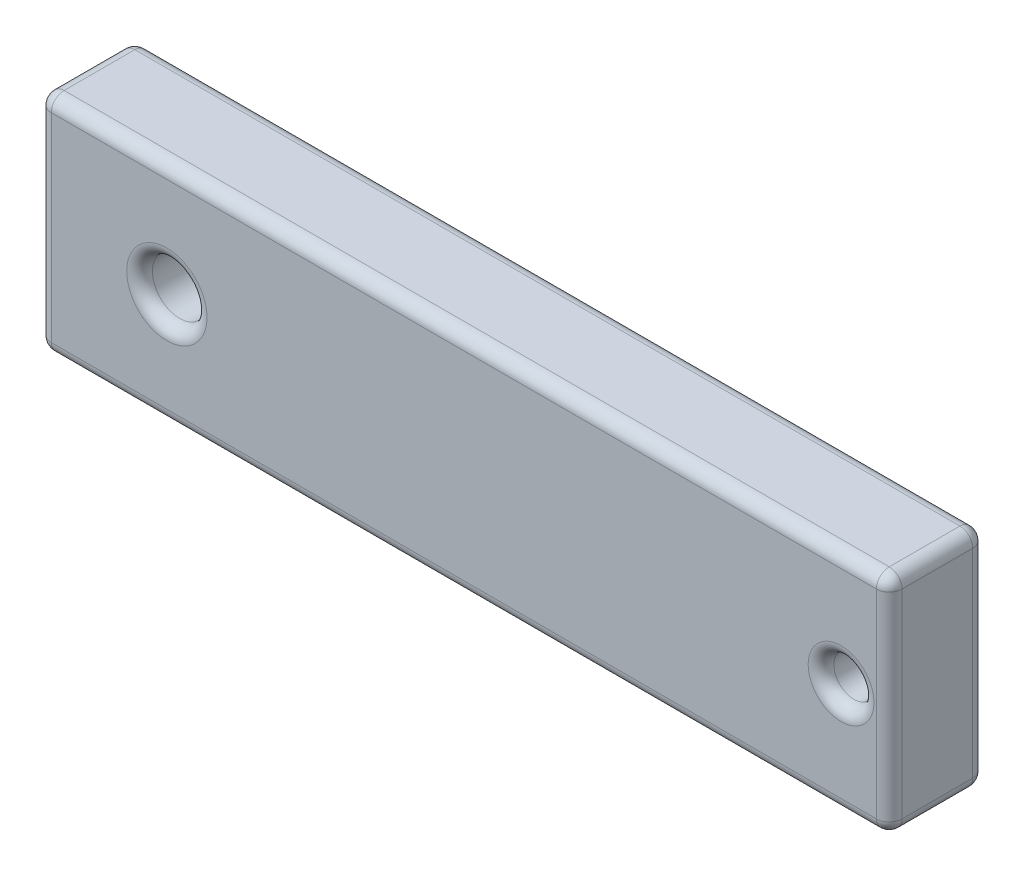
SolidWorks part; units mm, degrees
ref_plane "前视基准面" through (0, 0, 0) normal (0, 0, 1) x (1, 0, 0)
ref_plane "上视基准面" through (0, 0, 0) normal (0, 1, 0) x (1, 0, 0)
ref_plane "右视基准面" through (0, 0, 0) normal (1, 0, 0) x (0, 0, -1)
other "Configuration Table"
sketch "草图1" plane through (0, 0, 0) normal (0, 0, 1) x (1, 0, 0)
  line L1 (-8, -7) -> (45, -7)
  line L2 (-8, -7) -> (-8, 7)
  line L3 (-8, 7) -> (45, 7)
  line L4 (45, -7) -> (45, 7)
  line L5 (-8, -7) -> (45, 7) construction
  line L6 (-8, 7) -> (45, -7) construction
  circle A0 centre (0, 0) radius 1.7
  circle A1 centre (42, 0) radius 1.25
  point P0 (18.5, 0)
extrude "凸台-拉伸1" add sketch "草图1" along normal mid plane 6
sketch "草图2" plane through (0, 0, 0) normal (0, 0, 1) x (1, 0, 0)
  line L1 (-8, -30.25) -> (2, -30.25)
  line L2 (-8, -30.25) -> (-8, 7.25)
  line L3 (-8, 7.25) -> (2, 7.25)
  line L4 (2, -30.25) -> (2, 7.25)
  line L5 (-8, -30.25) -> (2, 7.25) construction
  line L6 (-8, 7.25) -> (2, -30.25) construction
fillet "圆角1" radius 0.8 16 edges at (43.25, 0, -3) (43.25, 0, 3) (1.7, 0, -3) (1.7, 0, 3) (45, 0, -3) (18.5, 7, -3) (-8, 0, -3) (18.5, -7, -3) (45, 0, 3) (18.5, 7, 3) (-8, 0, 3) (18.5, -7, 3) (45, -7, 0) (-8, -7, 0) (-8, 7, 0) (45, 7, 0) tangent propagation no
